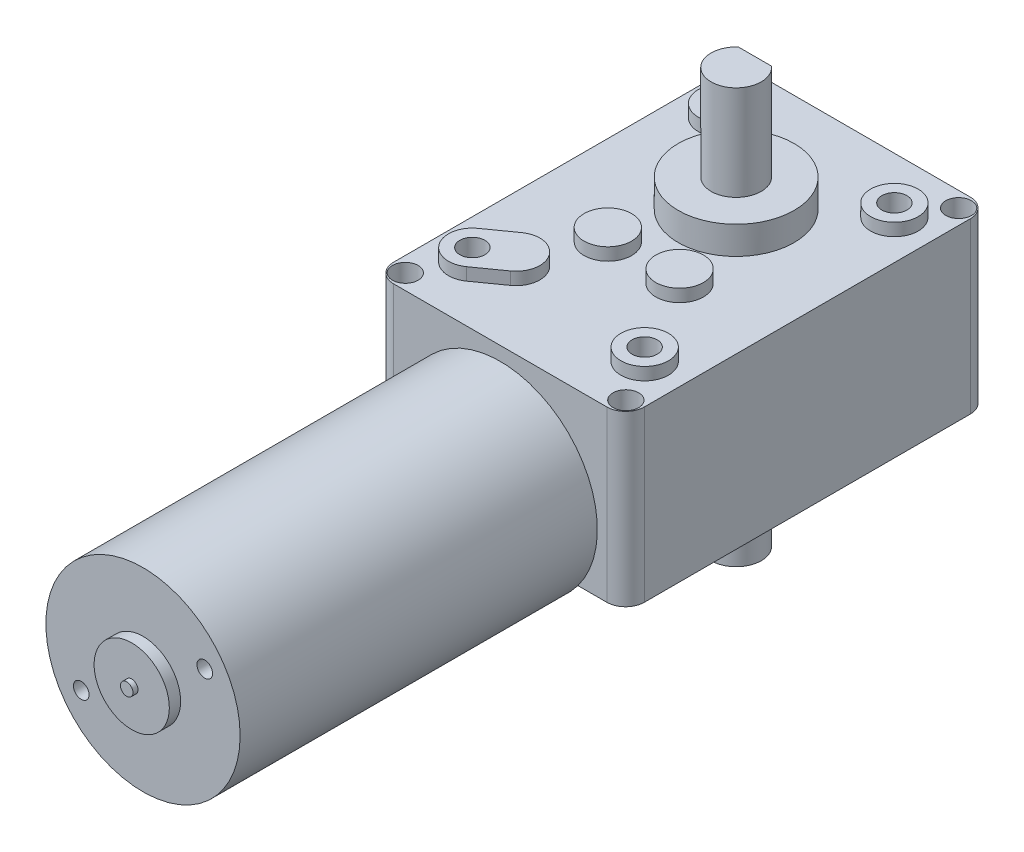
SolidWorks part; units mm, degrees
ref_plane "Front Plane" through (0, 0, 0) normal (0, 0, 1) x (1, 0, 0)
ref_plane "Top Plane" through (0, 0, 0) normal (0, 1, 0) x (1, 0, 0)
ref_plane "Right Plane" through (0, 0, 0) normal (1, 0, 0) x (0, 0, -1)
sketch "Sketch1" plane through (0, 0, 0) normal (0, 1, 0) x (1, 0, 0)
  line L1 (17.005, -29) -> (-17.005, -29)
  line L2 (20.005, -26) -> (20.005, 26)
  line L3 (17.005, 29) -> (-17.005, 29)
  line L4 (-20.005, -26) -> (-20.005, 26)
  line L5 (20.005, -29) -> (-20.005, 29) construction
  line L6 (20.005, 29) -> (-20.005, -29) construction
  arc A0 (-17.005, -29) -> (-20.005, -26) centre (-17.005, -26) cw
  arc A1 (17.005, -29) -> (20.005, -26) centre (17.005, -26) ccw
  arc A2 (20.005, 26) -> (17.005, 29) centre (17.005, 26) ccw
  arc A3 (-17.005, 29) -> (-20.005, 26) centre (-17.005, 26) ccw
  point P0 (0, 0)
  dimension "D1" = 40.01
  dimension "D2" = 58
  dimension "D3" = 3
extrude "Boss-Extrude2" add sketch "Sketch1" along normal blind 27
ref_plane "Plane1" through (0, 13.5, 0) normal (0, 1, 0) x (1, 0, 0)
sketch "Sketch5" plane through (0, 27, 0) normal (0, 1, 0) x (1, 0, 0)
  line L0 (-13.75, -19.7) -> (-9.6769, -16.8) construction
  line L1 (-15.954, -16.6045) -> (-11.8809, -13.7045)
  line L2 (-11.546, -22.7955) -> (-7.4729, -19.8955)
  line L3 (-17.005, -29) -> (17.005, -29) construction
  line L4 (0, -29) -> (0, 29) construction
  line L5 (17.005, 29) -> (-17.005, 29) construction
  line L6 (-17.005, -29) -> (17.005, -29) construction
  circle A0 centre (-13.75, 20.15) radius 3.8
  circle A1 centre (13.75, 20.15) radius 3.8
  circle A2 centre (13.75, -19.7) radius 3.8
  arc A3 (-15.954, -16.6045) -> (-11.546, -22.7955) centre (-13.75, -19.7) ccw
  arc A4 (-7.4729, -19.8955) -> (-11.8809, -13.7045) centre (-9.6769, -16.8) ccw
  circle A5 centre (-5.725, -6.1) radius 3.8
  circle A6 centre (5.725, -6.1) radius 3.8
  point P8 (-11.7135, -18.25)
  dimension "D2" = 5
  dimension "D5" = 11.45
  dimension "D7" = 22.9
  dimension "D6" = 7.6
  dimension "D8" = 7.6
  dimension "D1" = 7.6
  dimension "D3" = 39.85
  dimension "D4" = 9.3
  dimension "D9" = 27.5
  dimension "D10" = 12.2
extrude "Boss-Extrude3" add sketch "Sketch5" along normal blind 2
sketch "Sketch6" plane through (0, 29, 0) normal (0, 1, 0) x (1, 0, 0)
  circle A0 centre (13.75, -19.7) radius 2
  circle A1 centre (13.75, 20.15) radius 2
  circle A2 centre (-13.75, 20.15) radius 2
  circle A3 centre (-13.75, -19.7) radius 2
  arc A4 (-15.954, -16.6045) -> (-11.546, -22.7955) centre (-13.75, -19.7) ccw construction
  dimension "D1" = 4
extrude "Cut-Extrude3" cut sketch "Sketch6" against normal blind 4
sketch "Sketch7" plane through (0, 27, 0) normal (0, 1, 0) x (1, 0, 0)
  line L1 (17.005, 29) -> (-17.005, 29) construction
  circle A0 centre (0, 8.65) radius 9.25
  dimension "D1" = 18.5
  dimension "D2" = 20.35
extrude "Boss-Extrude4" add sketch "Sketch7" along normal blind 4.45
sketch "Sketch8" plane through (0, 31.45, 0) normal (0, 1, 0) x (1, 0, 0)
  circle A0 centre (0, 8.65) radius 4
  dimension "D1" = 8
extrude "Boss-Extrude5" add sketch "Sketch8" along normal blind 15.14
sketch "Sketch9" plane through (0, 46.59, 0) normal (0, 1, 0) x (1, 0, 0)
  line L0 (-2.6458, 11.65) -> (2.6458, 11.65)
  circle A0 centre (0, 8.65) radius 4 construction
  arc A1 (2.6458, 11.65) -> (-2.6458, 11.65) centre (0, 8.65) ccw
  dimension "D1" = 3
extrude "Cut-Extrude4" cut sketch "Sketch9" against normal blind 13
mirror "Mirror1" about plane through (0, 13.5, 0) normal (0, 1, 0) of "Cut-Extrude4", "Boss-Extrude5", "Boss-Extrude4", "Cut-Extrude3", "Boss-Extrude3"
sketch "Sketch11" plane through (0, 0, 29) normal (0, 0, 1) x (1, 0, 0)
  line L4 (-17.005, 0) -> (17.005, 0) construction
  circle A0 centre (0, 9.3) radius 15.5
  dimension "D1" = 31
  dimension "D2" = 9.3
extrude "Boss-Extrude6" add sketch "Sketch11" along normal blind 57
sketch "Sketch12" plane through (0, 0, 86) normal (0, 0, 1) x (1, 0, 0)
  circle A0 centre (0, 9.3) radius 6
  dimension "D1" = 12
extrude "Boss-Extrude7" add sketch "Sketch12" along normal blind 1.8
sketch "Sketch13" plane through (0, 0, 87.8) normal (0, 0, 1) x (1, 0, 0)
  circle A0 centre (0, 9.3) radius 1
  dimension "D1" = 2
extrude "Boss-Extrude8" add sketch "Sketch13" along normal blind 0.8
sketch "Sketch14" plane through (0, 0, 86) normal (0, 0, 1) x (1, 0, 0)
  line L0 (0, 9.3) -> (9.8544, 15.6995) construction
  line L1 (0, 9.3) -> (0, 24.8) construction
  circle A0 centre (0, 9.3) radius 11.75 construction
  circle A1 centre (9.8544, 15.6995) radius 1.25
  circle A3 centre (-9.8544, 2.9005) radius 1.25
  circle A4 centre (0, 9.3) radius 15.5 construction
  point P11 (0, 9.3)
  dimension "D1" = 23.5
  dimension "D2" = 57
  dimension "D3" = 2
  dimension "D4" = 2.5
extrude "Cut-Extrude6" cut sketch "Sketch14" against normal blind 4
sketch "Sketch10" plane through (0, 27, 0) normal (0, 1, 0) x (1, 0, 0)
  line L0 (0, 29) -> (0, -29) construction
  line L1 (17.005, 29) -> (-17.005, 29) construction
  line L2 (-17.005, -29) -> (17.005, -29) construction
  line L3 (-20.005, 0) -> (20.005, 0) construction
  line L4 (-20.005, 26) -> (-20.005, -26) construction
  line L5 (20.005, -26) -> (20.005, 26) construction
  circle A0 centre (-17.6, 26.55) radius 2.05
  circle A1 centre (17.6, 26.55) radius 2.05
  circle A2 centre (17.6, -26.55) radius 2.05
  circle A3 centre (-17.6, -26.55) radius 2.05
  dimension "D3" = 4.1
  dimension "D1" = 35.2
  dimension "D2" = 2.45
extrude "Cut-Extrude5" cut sketch "Sketch10" against normal blind 4
